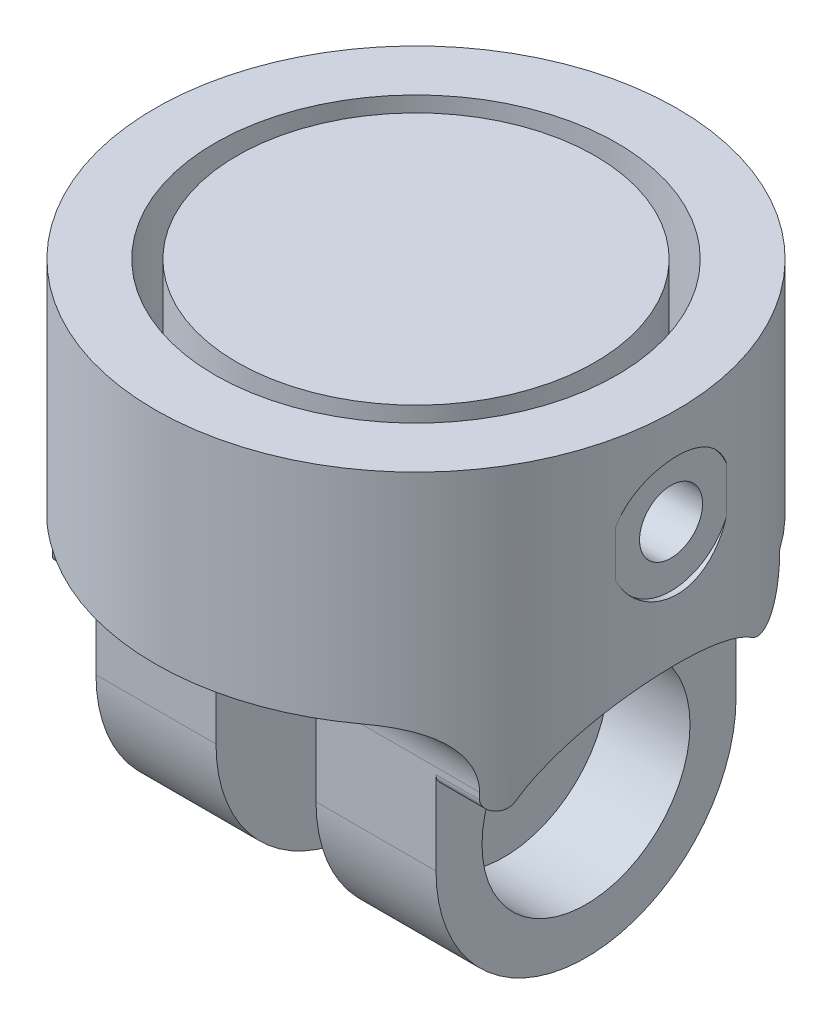
SolidWorks part; units mm, degrees
material "PLA Black"
ref_plane "Front" through (0, 0, 0) normal (0, 0, 1) x (1, 0, 0)
ref_plane "Top" through (0, 0, 0) normal (0, 1, 0) x (1, 0, 0)
ref_plane "Right" through (0, 0, 0) normal (1, 0, 0) x (0, 0, -1)
sketch "Sketch1" plane through (0, 0, 0) normal (0, 1, 0) x (1, 0, 0)
  line L0 (0, 8.95) -> (0, 10.05) construction
  circle A0 centre (0, 0) radius 10.05
  circle A1 centre (0, 0) radius 13.05
  circle A2 centre (0, 0) radius 9.5 construction
  circle A4 centre (0, 0) radius 8.95
  point P11 (0, 9.5)
  dimension "D1" = 1.1
  dimension "D2" = 3
  dimension "D3" = 19
extrude "Boss-Extrude1" add sketch "Sketch1" along normal blind 10 contours A1 A0 | A4 region at (-12.6809, 0, 0) region at (0, 0, 0)
sketch "Sketch3" plane through (0, 0, 0) normal (0, -1, 0) x (1, 0, 0)
  circle A2 centre (0, 0) radius 13.05 construction
  circle A3 centre (0, 0) radius 13.05
extrude "Boss-Extrude2" add sketch "Sketch3" along normal blind 1
sketch "Sketch4" plane through (0, -1, 0) normal (0, -1, 0) x (1, 0, 0)
  line L0 (0, 17.8908) -> (0, -17.0763) construction
  line L1 (2.5, 7.5) -> (8.5, 7.5)
  line L2 (2.5, 7.5) -> (2.5, -7.5)
  line L3 (2.5, -7.5) -> (8.5, -7.5)
  line L4 (8.5, 7.5) -> (8.5, -7.5)
  line L5 (-8.5, 7.5) -> (-8.5, -7.5)
  line L6 (-2.5, -7.5) -> (-8.5, -7.5)
  line L7 (-2.5, 7.5) -> (-2.5, -7.5)
  line L8 (-2.5, 7.5) -> (-8.5, 7.5)
  line L9 (16.8049, 0) -> (-19.8998, 0) construction
  dimension "D1" = 6
  dimension "D2" = 5
  dimension "D3" = 15
extrude "Boss-Extrude3" add sketch "Sketch4" along normal blind 15
sketch "Sketch5" plane through (8.5, 0, 0) normal (1, 0, 0) x (0, 0, -1)
  line L0 (-7.5, -16) -> (-7.5, -1) construction
  line L1 (7.5, -16) -> (7.5, -1) construction
  line L2 (7.5, -8.5) -> (7.5, -17.1619)
  line L3 (7.5, -17.1619) -> (-7.5, -17.1619)
  line L4 (-7.5, -17.1619) -> (-7.5, -8.5)
  arc A0 (-7.5, -8.5) -> (7.5, -8.5) centre (0, -8.5) ccw
  circle A1 centre (0, -8.5) radius 1.55
  dimension "D1" = 3.1
extrude "Cut-Extrude1" cut sketch "Sketch5" against normal through all both and the other way through all
sketch "Sketch6" plane through (8.5, 0, 0) normal (1, 0, 0) x (0, 0, -1)
  circle A0 centre (0, -8.5) radius 5.2
  dimension "D1" = 10.4
extrude "Cut-Extrude2" cut sketch "Sketch6" against normal blind 4.1
mirror "Mirror1" about plane through (0, 0, 0) normal (1, 0, 0) of "Cut-Extrude2"
ref_plane "Plane9" through (1.335, 0, 0) normal (1, 0, 0) x (0, 0, -1)
sketch "Sketch7" plane through (1.335, 0, 0) normal (1, 0, 0) x (0, 0, -1)
  line L0 (3.555, -8.5) -> (3.555, -1) construction
  line L1 (7.5, -1) -> (-7.5, -1) construction
  line L2 (3.4474, -7.632) -> (1.7775, -1) construction
  line L3 (3.1303, -6.8149) -> (0, -1) construction
  line L4 (1.7775, -0.6757) -> (1.7775, -1.4422) construction
  line L5 (2.6911, -6.1771) -> (-1.7775, -1) construction
  line L6 (2.2506, -5.7481) -> (-3.555, -1) construction
  line L8 (0, -1.6788) -> (0, 0) construction
  line L9 (-8.4824, -8.5) -> (8.712, -8.5) construction
  line L10 (1.8766, -5.4807) -> (-5.3325, -1) construction
  line L11 (-3.555, -0.3587) -> (-3.555, -1.6788) construction
  circle A0 centre (0, -8.5) radius 3.555 construction
  dimension "D1" = 7.11
  dimension "D2" = 31.862
  dimension "D3" = 7.5
ref_plane "Plane1" through (1.335, -1, -3.555) normal (0, 1, 0) x (1, 0, 0)
ref_plane "Plane2" through (1.335, -1, -1.7775) normal (0, 0.9697, 0.2442) x (1, 0, 0)
ref_plane "Plane3" through (1.335, -1, 0) normal (0, 0.8805, 0.474) x (1, 0, 0)
ref_plane "Plane5" through (1.335, -1, 1.7775) normal (0, 0.757, 0.6534) x (1, 0, 0)
ref_plane "Plane6" through (1.335, -1, 3.555) normal (0, 0.6331, 0.7741) x (1, 0, 0)
ref_plane "Plane7" through (1.335, -1, 5.3325) normal (0, 0.5279, 0.8493) x (1, 0, 0)
sketch "Sketch8" plane through (1.335, -1, -3.555) normal (0, 1, 0) x (1, 0, 0)
  circle A0 centre (0, 0) radius 0.4895
  dimension "D1" = 0.979
extrude "Cut-Extrude5" cut sketch "Sketch8" along normal blind 5.5 and the other way through all
sketch "Sketch9" plane through (1.335, -1, -1.7775) normal (0, 0.9697, 0.2442) x (1, 0, 0)
  circle A0 centre (0, 0) radius 0.4895
  dimension "D1" = 0.979
extrude "Cut-Extrude3" cut sketch "Sketch9" along normal blind 5.5
sketch "Sketch10" plane through (1.335, -1, 0) normal (0, 0.8805, 0.474) x (1, 0, 0)
  circle A0 centre (0, 0) radius 0.4895
  dimension "D1" = 0.979
sketch "Sketch11" plane through (1.335, -1, 1.7775) normal (0, 0.757, 0.6534) x (1, 0, 0)
  circle A0 centre (0, 0) radius 0.4895
  dimension "D1" = 0.979
sketch "Sketch12" plane through (1.335, -1, 3.555) normal (0, 0.6331, 0.7741) x (1, 0, 0)
  circle A0 centre (0, 0) radius 0.4895
  dimension "D1" = 0.979
sketch "Sketch14" plane through (1.335, -1, 5.3325) normal (0, 0.5279, 0.8493) x (1, 0, 0)
  circle A0 centre (0, 0) radius 0.4895
  dimension "D1" = 0.979
extrude "Cut-Extrude6" cut sketch "Sketch10" along normal blind 5.5 and the other way through all
extrude "Cut-Extrude7" cut sketch "Sketch11" along normal blind 5.5 and the other way through all contours A0
extrude "Cut-Extrude8" cut sketch "Sketch12" along normal blind 5.5 and the other way through all contours A0
extrude "Cut-Extrude9" cut sketch "Sketch14" along normal blind 5.5 and the other way through all contours A0
ref_plane "Plane8" through (13.05, 0, 0) normal (1, 0, 0) x (0, 0, -1)
hole_wizard "Tap Drill for M3 Helicoil1" positions "Sketch17" profile "Sketch18" hole size "M3x0.5" standard "DIN"
sketch "Sketch17" plane through (13.05, 0, 0) normal (1, 0, 0) x (0, 0, -1)
  line L0 (-22.2973, 5) -> (18.0703, 5) construction
  line L4 (0, 12.2732) -> (0, -5.3405) construction
  line L6 (-7.5, -8.5) -> (-7.5, -1) construction
  line L7 (7.5, -8.5) -> (7.5, -1) construction
  line L8 (13.05, 10) -> (-13.05, 10) construction
  line L9 (10.05, 0) -> (-10.05, 0) construction
  point P0 (0, 5)
sketch "Sketch18" plane through (13.05, 5, 0) normal (0, 1, 0) x (0, 0, -1)
  line L0 (0, 0) -> (0, 6.9464)
  line L1 (0, 6.9464) -> (1.575, 6)
  line L2 (1.575, 6) -> (1.575, 0)
  line L5 (1.575, 0) -> (0, 0)
  line L10 (0, 6.9464) -> (-1.575, 6) construction
  line L11 (0, -6.35) -> (0, 107.95) construction
  dimension "Hole Dia." = 3.15
  dimension "Hole Depth" = 6
  dimension "Drill Angle" = 118
sketch "Sketch20" plane through (13.05, 0, 0) normal (1, 0, 0) x (0, 0, -1)
  circle A0 centre (0, 5) radius 3
  dimension "D1" = 6
extrude "Cut-Extrude10" cut sketch "Sketch20" against normal blind 0.3
sketch "Sketch21" plane through (8.5, 0, 0) normal (1, 0, 0) x (0, 0, -1)
  line L0 (7.5, -1) -> (-7.5, -1) construction
  line L1 (7.5, -0.1252) -> (7.5, -1.1767)
  line L2 (0.9244, -19.0662) -> (-4.8209, -14.2453) construction
  line L3 (0, 5.2718) -> (0, -9.2894) construction
  line L4 (0, 10) -> (0, -1) construction
  line L5 (-7.5, -0.1252) -> (-7.5, -4.3226)
  line L6 (7.5, -0.1252) -> (-7.5, -0.1252)
  line L7 (-7.5, -8.5) -> (-7.5, -1) construction
  line L8 (7.5, -8.5) -> (7.5, -1) construction
  line L9 (0, -1) -> (9.4693, -4.4465) construction
  line L10 (0, -1) -> (1.6171, -0.0664) construction
  line L11 (4.6128, -2.5863) -> (7.5, -1.1767) construction
  line L12 (10.5662, -7.5756) -> (4.8209, -2.7547) construction
  line L13 (-4.8209, -14.2453) -> (4.8209, -2.7547) construction
  line L14 (10.5662, -7.5756) -> (0.9244, -19.0662) construction
  arc A0 (-6.4204, -4.6233) -> (4.6128, -2.5863) centre (0, -8.5) cw
  arc A1 (-6.4204, -4.6233) -> (-7.5, -4.3226) centre (-6.9183, -4.3226) cw
  arc A2 (7.5, -1.1767) -> (4.6128, -2.5863) centre (5.7123, -1.1767) cw
  circle A3 centre (0, -8.5) radius 1.55 construction
  arc A4 (-4.8209, -14.2453) -> (4.8209, -2.7547) centre (0, -8.5) cw construction
  dimension "D1" = 30
  dimension "D3" = 7.5
  dimension "D2" = 50
  dimension "D4" = 15
extrude "Boss-Extrude4" add sketch "Sketch21" along normal up to surface (2.1795 mm away) up to face at (12.895, 5, 0)
mirror "Mirror2" about plane through (0, 0, 0) normal (1, 0, 0) of "Boss-Extrude4", "Tap Drill for M3 Helicoil1", "Cut-Extrude10"
fillet "Fillet1" radius 3 2 edges at (-6.5898, -1, 7.5) (6.5898, -1, 7.5)
equation "\"knee_angle\"= 70"
equation "\"ankle_angle\" = 90"
equation "\"hip_angle\" = 30"
equation "\"spring_ankle_parallel_arm_diameter\"= 0.89"
equation "\"spring_ankle_parallel_arm_length\"= 13"
equation "\"spring_ankle_parallel_intern_diameter\"= 6.22"
equation "\"spring_ankle_parallel_angle\"= \"ankle_angle\""
equation "\"spring_ankle_parallel_turns\"= 3"
equation "\"spring_ankle_parallel_pitch\"= \"spring_ankle_parallel_arm_diameter\" * 1.01"
equation "\"spring_ankle_parallel_cutting_distance\"= (1-\"spring_ankle_parallel_angle\" / 360) * \"spring_ankle_parallel_pitch\""
equation "\"spring_ankle_serial_arm_diameter\"= 0.89"
equation "\"spring_ankle_serial_arm_length\"= 10"
equation "\"spring_ankle_serial_intern_diameter\"= 6.22"
equation "\"spring_ankle_serial_angle\"= \"90\""
equation "\"spring_ankle_serial_turns\"= 3"
equation "\"spring_ankle_serial_pitch\"= \"spring_ankle_serial_arm_diameter\" * 1.01"
equation "\"spring_ankle_serial_cutting_distance\"= (1-\"spring_ankle_serial_angle\" / 360) * \"spring_ankle_serial_pitch\""
equation "\"spring_knee_parallel_arm_diameter\"= 0.43"
equation "\"spring_knee_parallel_arm_length\"= 15"
equation "\"spring_knee_parallel_intern_diameter\"= 5.46"
equation "\"spring_knee_parallel_angle\"= \"knee_angle\""
equation "\"spring_knee_parallel_turns\"= 3"
equation "\"spring_knee_parallel_pitch\"= \"spring_knee_parallel_arm_diameter\" * 1.01"
equation "\"spring_knee_parallel_cutting_distance\"= (1-\"spring_knee_parallel_angle\" / 360) * \"spring_knee_parallel_pitch\""
equation "\"spring_knee_serial_arm_diameter\"= 0.43"
equation "\"spring_knee_serial_arm_length\"= 10"
equation "\"spring_knee_serial_intern_diameter\"= 5.46"
equation "\"spring_knee_serial_angle\"= \"90\""
equation "\"spring_knee_serial_turns\"= 3"
equation "\"spring_knee_serial_pitch\"= \"spring_knee_serial_arm_diameter\" * 1.01"
equation "\"spring_knee_serial_cutting_distance\"= (1-\"spring_knee_serial_angle\" / 360) * \"spring_knee_serial_pitch\""
equation "\"spring_ankle_parallel_nominal_diameter\"= \"spring_ankle_parallel_arm_diameter\" + \"spring_ankle_parallel_intern_diameter\""
equation "\"spring_ankle_serial_nominal_diameter\"= \"spring_ankle_serial_arm_diameter\" + \"spring_ankle_serial_intern_diameter\""
equation "\"spring_knee_parallel_nominal_diameter\"= \"spring_knee_parallel_arm_diameter\" + \"spring_knee_parallel_intern_diameter\""
equation "\"spring_knee_serial_nominal_diameter\"= \"spring_knee_serial_arm_diameter\" + \"spring_knee_serial_intern_diameter\""
equation "\"D1@Sketch7\"=\"spring_ankle_parallel_nominal_diameter\""
equation "\"D1@Sketch8\"=\"spring_ankle_parallel_arm_diameter\"*1.1"
equation "\"D1@Sketch9\"=\"spring_ankle_parallel_arm_diameter\"*1.1"
equation "\"D1@Sketch10\"=\"spring_ankle_parallel_arm_diameter\"*1.1"
equation "\"D1@Sketch11\"=\"spring_ankle_parallel_arm_diameter\"*1.1"
equation "\"D1@Sketch12\"=\"spring_ankle_parallel_arm_diameter\"*1.1"
equation "\"D1@Sketch14\"=\"spring_ankle_parallel_arm_diameter\"*1.1"
equation "\"D1@Cut-Extrude3\"=\"spring_ankle_parallel_arm_length\"-\"axis_structure_distance\""
equation "\"axis_structure_distance\"= 7.5"
equation "\"D1@Cut-Extrude5\"=\"spring_ankle_parallel_arm_length\"-\"axis_structure_distance\""
equation "\"D1@Cut-Extrude6\"=\"spring_ankle_parallel_arm_length\"-\"axis_structure_distance\""
equation "\"D1@Cut-Extrude7\"=\"spring_ankle_parallel_arm_length\"-\"axis_structure_distance\""
equation "\"D1@Cut-Extrude8\"=\"spring_ankle_parallel_arm_length\"-\"axis_structure_distance\""
equation "\"D1@Cut-Extrude9\"=\"spring_ankle_parallel_arm_length\"-\"axis_structure_distance\""
equation "\"D1@Boss-Extrude3\"=\"axis_structure_distance\"*2"
equation "\"ankle_angle_max\" = 120"
equation "\"ankle_angle_min\" = 50"
equation "\"knee_angle_max\" = 120"
equation "\"knee_angle_min\" = 0"
equation "\"hip_angle_max\" = 45"
equation "\"hip_angle_min\" = -45"
equation "\"D1@Sketch21\"=\"ankle_angle_max\"-90"
equation "\"D2@Sketch21\"=\"ankle_angle_min\""
equation "\"D1@Plane9\"=(\"spring_ankle_parallel_arm_diameter\"*\"spring_ankle_parallel_turns\")/2"
